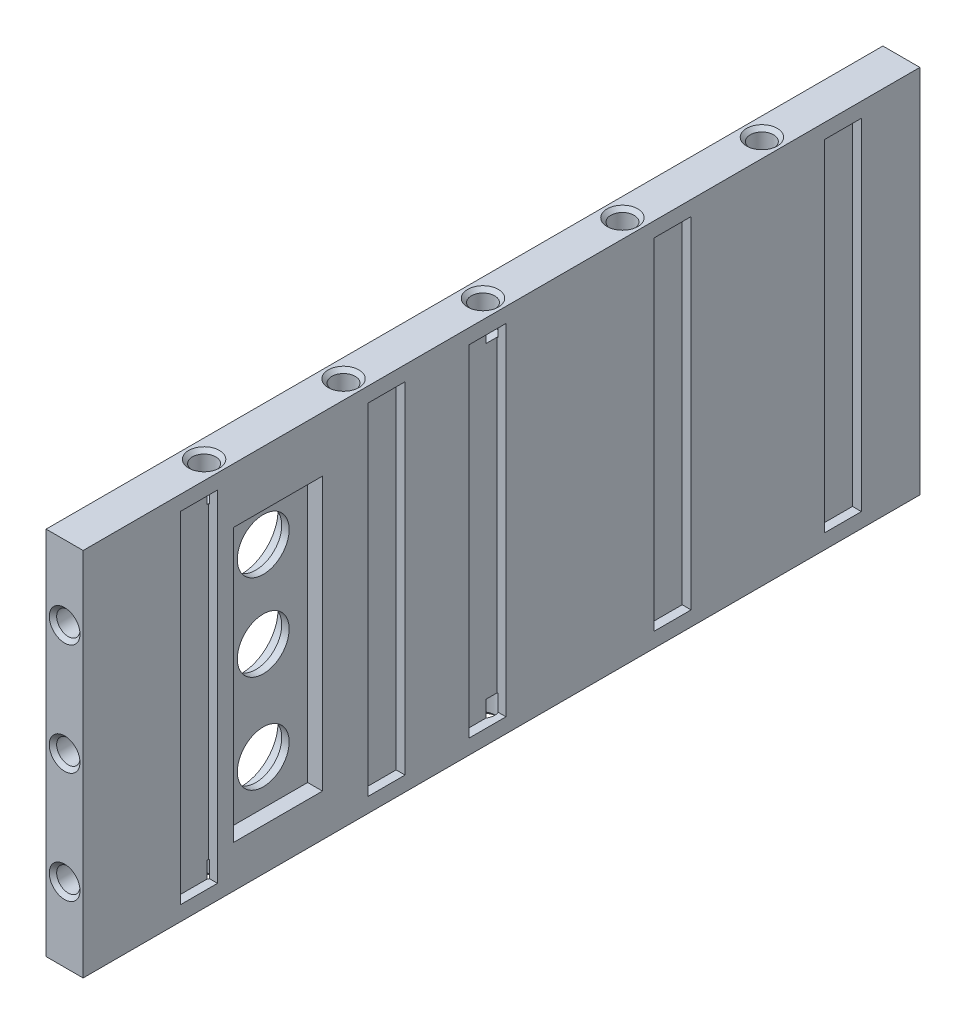
SolidWorks part; units mm, degrees
ref_plane "Спереди" through (0, 0, 0) normal (0, 0, 1) x (1, 0, 0)
ref_plane "Сверху" through (0, 0, 0) normal (0, 1, 0) x (1, 0, 0)
ref_plane "Справа" through (0, 0, 0) normal (1, 0, 0) x (0, 0, -1)
sketch "Эскиз1" plane through (0, 0, 0) normal (1, 0, 0) x (0, 0, -1)
  line L1 (-113, 25) -> (0, 25)
  line L2 (-113, 25) -> (-113, -25)
  line L3 (-113, -25) -> (0, -25)
  line L4 (0, 25) -> (0, -25)
  point P4 (0, 0)
  dimension "D1" = 113
  dimension "D2" = 50
extrude "Бобышка-Вытянуть1" add sketch "Эскиз1" along normal blind 5
ref_plane "Плоскость1" through (0, 0, 0) normal (0, -1, 0) x (-1, 0, 0)
sketch "Эскиз2" plane through (0, -25, 0) normal (0, -1, 0) x (1, 0, 0)
  line L0 (2.5, 113) -> (2.5, 94.1667) construction
  line L1 (5, 113) -> (0, 113) construction
  line L2 (2.5, 94.1667) -> (2.5, 75.3333) construction
  line L3 (2.5, 75.3333) -> (2.5, 56.5) construction
  line L4 (2.5, 56.5) -> (2.5, 37.6667) construction
  line L5 (2.5, 37.6667) -> (2.5, 18.8333) construction
  line L6 (2.5, 18.8333) -> (2.5, 0) construction
  line L7 (5, 0) -> (0, 0) construction
  line L8 (5, 113) -> (5, 0) construction
  circle A0 centre (2.5, 94.1667) radius 1.575
  circle A1 centre (2.5, 75.3333) radius 1.575
  circle A2 centre (2.5, 56.5) radius 1.575
  circle A3 centre (2.5, 37.6667) radius 1.575
  circle A4 centre (2.5, 18.8333) radius 1.575
  dimension "D3" = 3.15
  dimension "D2" = 2.5
  dimension "D1" = 5
extrude "Крепежные отверстия верхней и нижней крышки" cut sketch "Эскиз2" against normal blind 4.2
mirror "Зеркальное отражение1" about plane through (0, 0, 0) normal (0, -1, 0) of "Крепежные отверстия верхней и нижней крышки"
ref_plane "Плоскость2" through (0, 0, 56.5) normal (0, 0, -1) x (-1, 0, 0)
sketch "Эскиз3" plane through (0, 0, 113) normal (0, 0, 1) x (1, 0, 0)
  line L0 (-2.9169, 30) -> (11.1229, 30) construction
  line L1 (-5.1832, -30) -> (8.8566, -30) construction
  line L2 (5, 25) -> (5, 30) construction
  line L3 (5, -25) -> (5, -30) construction
  line L4 (2.5, 30) -> (2.5, 15) construction
  line L5 (2.5, 15) -> (2.5, 0) construction
  line L6 (2.5, 0) -> (2.5, -15) construction
  line L7 (2.5, -15) -> (2.5, -30) construction
  line L8 (5, 25) -> (5, -25) construction
  circle A0 centre (2.5, 15) radius 1.575
  circle A1 centre (2.5, 0) radius 1.575
  circle A2 centre (2.5, -15) radius 1.575
  dimension "D4" = 3.15
  dimension "D1" = 5
  dimension "D3" = 2.5
  dimension "D2" = 3
extrude "Крепежные отверстия лицевой и задней стороны" cut sketch "Эскиз3" against normal blind 4.2
mirror "Зеркальное отражение2" about plane through (0, 0, 56.5) normal (0, 0, -1) of "Крепежные отверстия лицевой и задней стороны"
sketch "Эскиз4" plane through (5, 0, 0) normal (1, 0, 0) x (0, 0, -1)
  line L0 (-5.9, 41.7127) -> (-5.9, -32.2038) construction
  line L1 (0, -25) -> (0, 25) construction
  line L2 (-7.9, 23) -> (-7.9, 25) construction
  line L3 (-12.9, 23) -> (-7.9, 23)
  line L4 (-12.9, 23) -> (-12.9, -23)
  line L5 (-12.9, -23) -> (-7.9, -23)
  line L6 (-7.9, 23) -> (-7.9, -23)
  line L7 (0, 25) -> (-113, 25) construction
  line L8 (-7.9, -23) -> (-7.9, -25) construction
  line L9 (-113, -25) -> (0, -25) construction
  line L10 (-21.9, 29.9409) -> (-21.9, -27.9732) construction
  line L11 (-45.9, 27.9425) -> (-45.9, -29.5532) construction
  line L12 (-35.9, 23) -> (-35.9, -23)
  line L13 (-30.9, -23) -> (-35.9, -23)
  line L14 (-30.9, 23) -> (-30.9, -23)
  line L15 (-30.9, 23) -> (-35.9, 23)
  line L16 (-60.9, 23) -> (-55.9, 23)
  line L17 (-60.9, 23) -> (-60.9, -23)
  line L18 (-60.9, -23) -> (-55.9, -23)
  line L19 (-55.9, 23) -> (-55.9, -23)
  line L20 (-65.215, 29.9409) -> (-65.215, -28.7246) construction
  line L21 (-74.53, 23) -> (-74.53, -23)
  line L22 (-69.53, -23) -> (-74.53, -23)
  line L23 (-69.53, 23) -> (-69.53, -23)
  line L24 (-69.53, 23) -> (-74.53, 23)
  line L25 (-84.69, 29.9409) -> (-84.69, -31.641) construction
  line L26 (-99.85, 23) -> (-94.85, 23)
  line L27 (-99.85, 23) -> (-99.85, -23)
  line L28 (-99.85, -23) -> (-94.85, -23)
  line L29 (-94.85, 23) -> (-94.85, -23)
  dimension "D1" = 5.9
  dimension "D2" = 5
  dimension "D3" = 2
  dimension "D4" = 46
  dimension "D5" = 23
  dimension "D6" = 25
  dimension "D7" = 13.63
  dimension "D8" = 25.32
extrude "Выбор под контакты" cut sketch "Эскиз4" against normal blind 1.2
sketch "Эскиз5" plane through (5, 0, 0) normal (1, 0, 0) x (0, 0, -1)
  line L0 (-86.68, 31.4583) -> (-86.68, -34.9653) construction
  line L1 (0, 25) -> (-113, 25) construction
  line L2 (-69.53, -23) -> (-69.53, 23) construction
  circle A0 centre (-86.68, 11.54) radius 3.5
  circle A1 centre (-86.68, -0.09) radius 3.5
  circle A2 centre (-86.68, -13.3) radius 3.5
  dimension "D1" = 7
  dimension "D2" = 13.46
  dimension "D3" = 11.63
  dimension "D4" = 13.21
  dimension "D5" = 17.15
extrude "SMA раземы" cut sketch "Эскиз5" against normal through all
sketch "Эскиз6" plane through (0, 0, 0) normal (-1, 0, 0) x (0, 0, 1)
  circle A0 centre (86.68, 11.54) radius 5
  circle A1 centre (86.68, -0.09) radius 5
  circle A2 centre (86.68, -13.3) radius 5
  dimension "D1" = 10
extrude "SMA раземы2" cut sketch "Эскиз6" against normal blind 2
sketch "Эскиз7" plane through (5, 0, 0) normal (1, 0, 0) x (0, 0, -1)
  line L1 (-80.68, 17.54) -> (-92.68, 17.54)
  line L2 (-80.68, 17.54) -> (-80.68, -19.3)
  line L3 (-80.68, -19.3) -> (-92.68, -19.3)
  line L4 (-92.68, 17.54) -> (-92.68, -19.3)
  circle A0 centre (-86.68, -13.3) radius 3.5 construction
  circle A1 centre (-86.68, 11.54) radius 3.5 construction
  dimension "D1" = 6
  dimension "D2" = 6
  dimension "D3" = 6
  dimension "D4" = 6
extrude "SMA раземы3" cut sketch "Эскиз7" against normal blind 2
chamfer "Фаска под запресовку" distance 0.5 angle 45 16 edges at (4.075, 15, 0) (4.075, 0, 0) (4.075, -15, 0) (2.5, -25, 17.2583) (2.5, -25, 36.0917) (2.5, -25, 54.925) (2.5, -25, 73.7583) (2.5, -25, 92.5917) (4.075, -15, 113) (4.075, 0, 113) (4.075, 15, 113) (2.5, 25, 92.5917) (2.5, 25, 73.7583) (2.5, 25, 54.925) (2.5, 25, 36.0917) (2.5, 25, 17.2583)
